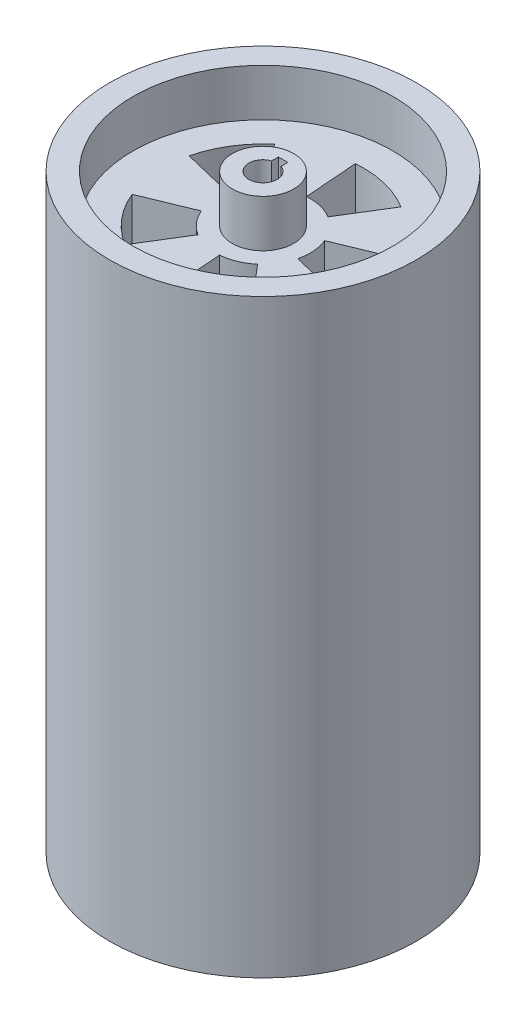
SolidWorks part; units mm, degrees
material "Plain Carbon Steel"
ref_plane "Front Plane" through (0, 0, 0) normal (0, 0, 1) x (1, 0, 0)
ref_plane "Top Plane" through (0, 0, 0) normal (0, 1, 0) x (1, 0, 0)
ref_plane "Right Plane" through (0, 0, 0) normal (1, 0, 0) x (0, 0, -1)
sketch "Sketch1" plane through (0, 0, 0) normal (0, 1, 0) x (1, 0, 0)
  line L1 (-2.5, 8.5) -> (2.5, 8.5)
  line L2 (-2.5, 8.5) -> (-2.5, 5.4544)
  line L4 (2.5, 8.5) -> (2.5, 5.4544)
  line L5 (-2.5, 8.5) -> (4.1708, 1.8292) construction
  line L6 (-4.1708, 1.8292) -> (2.5, 8.5) construction
  circle A0 centre (0, 0) radius 55
  circle A1 centre (0, 0) radius 65
  arc A2 (-2.5, 5.4544) -> (2.5, 5.4544) centre (0, 0) ccw
  point P4 (0, 8.5)
  point P5 (0, 6)
  dimension "D1" = 5
  dimension "D3" = 12
  dimension "D4" = 130
  dimension "D5" = 110
  dimension "D2" = 2.5
  dimension "D6" = 3.0456
extrude "Boss-Extrude1" add sketch "Sketch1" along normal blind 250 contours A1 A0 region at (-63.1615, 0, 0)
sketch "Sketch3" plane through (0, 0, 0) normal (0, 1, 0) x (1, 0, 0)
  line L1 (41.3049, -10.0079) -> (19.4376, -4.7096)
  line L2 (18.4936, 7.615) -> (39.2988, 16.1819)
  line L3 (19.4376, -4.7096) -> (41.3049, -10.0079)
  line L4 (3.2459, -42.3759) -> (1.5275, -19.9416)
  line L5 (12.9571, -15.2353) -> (27.5339, -32.3749)
  line L6 (-39.2988, -16.1819) -> (-18.4936, -7.615)
  line L7 (-10.4856, -17.0309) -> (-22.2819, -36.1907)
  line L8 (-27.5339, 32.3749) -> (-12.9571, 15.2353)
  line L9 (-19.4376, 4.7096) -> (-41.3049, 10.0079)
  line L10 (22.2819, 36.1907) -> (10.4856, 17.0309)
  line L11 (-1.5275, 19.9416) -> (-3.2459, 42.3759)
  line L18 (2, 5.6569) -> (2, 8.5)
  line L19 (2, 8.5) -> (-2, 8.5)
  line L20 (-2, 5.6569) -> (-2, 8.5)
  line L21 (2.5047, 2.8691) -> (-2, 8.5) construction
  line L22 (2, 8.5) -> (-2.5047, 2.8691) construction
  circle A0 centre (0, 0) radius 6.5
  circle A1 centre (0, 0) radius 55
  arc A2 (41.3049, -10.0079) -> (39.2988, 16.1819) centre (0, 0) ccw
  circle A3 centre (0, 0) radius 20
  circle A4 centre (0, 0) radius 13
  arc A5 (3.2459, -42.3759) -> (27.5339, -32.3749) centre (0, 0) ccw
  arc A6 (-39.2988, -16.1819) -> (-22.2819, -36.1907) centre (0, 0) ccw
  arc A7 (-27.5339, 32.3749) -> (-41.3049, 10.0079) centre (0, 0) ccw
  arc A8 (22.2819, 36.1907) -> (-3.2459, 42.3759) centre (0, 0) ccw
  arc A9 (-2, 5.6569) -> (2, 5.6569) centre (0, 0) ccw
  point P28 (0, 6)
  dimension "D1" = 110
  dimension "D2" = 85
  dimension "D3" = 40
  dimension "D4" = 13
  dimension "D7" = 26
  dimension "D8" = 4
  dimension "D10" = 12
  dimension "D5" = 20.8053
  dimension "D6" = 21.8673
  dimension "D9" = 2.5
  dimension "D11" = 2.8431
extrude "Boss-Extrude2" add sketch "Sketch3" along normal blind 20 from offset 20 contours A1 A8 L10 A3 L2 A2 L1 L5 A5 L4 L7 A6 L6 L9 A7 L8 L11 | A3 A4 region at (16.5492, 0, 10.189) region at (-53.4444, 0, 0)
extrude "Boss-Extrude3" add sketch "Sketch3<5>" along normal blind 20 from offset 210 contours A1 A8 L10 A3 L2 A2 L1 L5 A5 L4 L7 A6 L6 L9 A7 L8 L11 | A3 A4 region at (16.5492, 0, 10.189) region at (-53.4444, 0, 0)
sketch "Sketch3<5>" plane through (0, 0, 0) normal (0, 1, 0) x (1, 0, 0) same geometry as "Sketch3"
extrude "Boss-Extrude4" add sketch "Sketch3<7>" along normal blind 210 from offset 20 contours A4 A0 L20 L19 L18 | A0 L18 L19 L20 region at (0, 0, -7.4459) region at (-12.6323, 0, 0)
sketch "Sketch3<7>" plane through (0, 0, 0) normal (0, 1, 0) x (1, 0, 0) same geometry as "Sketch3"
extrude "Boss-Extrude5" add sketch "Sketch3<10>" along normal blind 20 contours A9 L20 A0 L18 | A4 A0 L20 L19 L18 region at (2.1816, 0, -5.9208) region at (-12.6323, 0, 0)
sketch "Sketch3<10>" plane through (0, 0, 0) normal (0, 1, 0) x (1, 0, 0) same geometry as "Sketch3"
extrude "Boss-Extrude6" add sketch "Sketch3<11>" along normal blind 20 from offset 230 contours A9 L20 A0 L18 | A4 A0 L20 L19 L18 region at (2.1816, 0, -5.9208) region at (-12.6323, 0, 0)
sketch "Sketch3<11>" plane through (0, 0, 0) normal (0, 1, 0) x (1, 0, 0) same geometry as "Sketch3"
